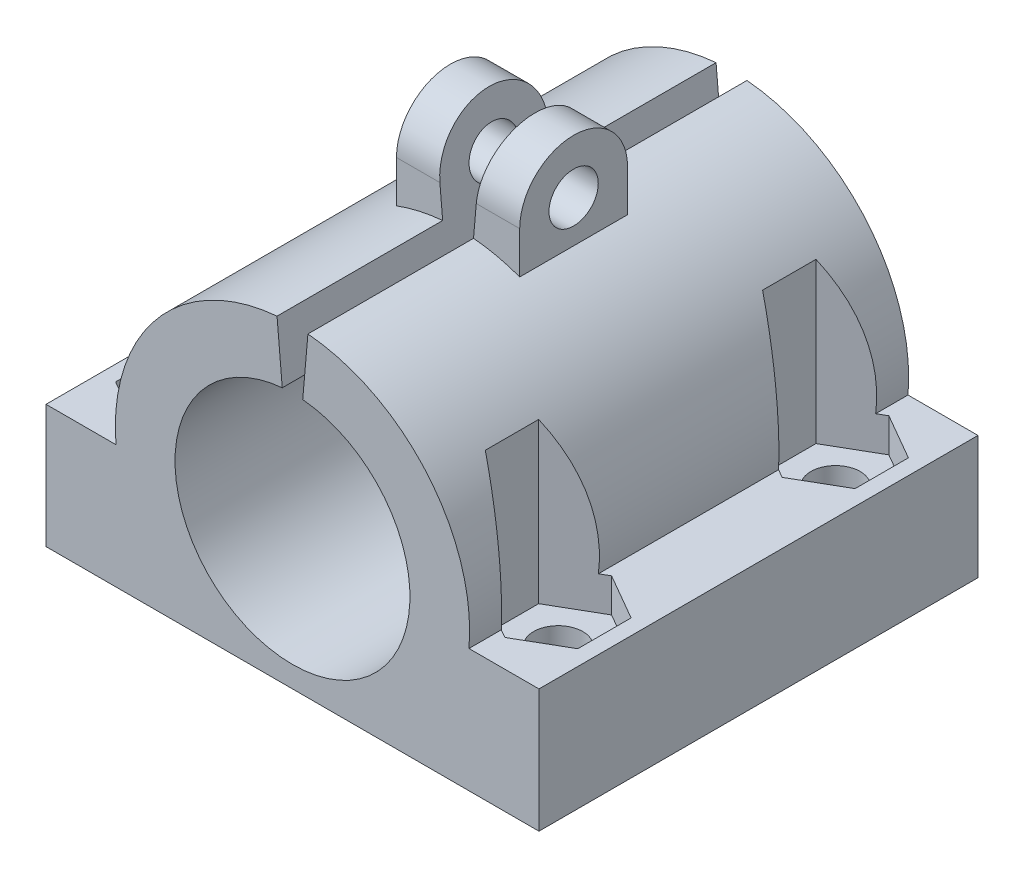
SolidWorks part; units mm, degrees
ref_plane "Front Plane" through (0, 0, 0) normal (0, 0, 1) x (1, 0, 0)
ref_plane "Top Plane" through (0, 0, 0) normal (0, 1, 0) x (1, 0, 0)
ref_plane "Right Plane" through (0, 0, 0) normal (1, 0, 0) x (0, 0, -1)
sketch "Sketch1" plane through (0, 0, 0) normal (0, 1, 0) x (1, 0, 0)
  line L1 (-16, 14.25) -> (16, 14.25)
  line L2 (-16, 14.25) -> (-16, -14.25)
  line L3 (-16, -14.25) -> (16, -14.25)
  line L4 (16, 14.25) -> (16, -14.25)
  line L5 (-16, 14.25) -> (16, -14.25) construction
  line L6 (-16, -14.25) -> (16, 14.25) construction
  point P0 (0, 0)
  dimension "D1" = 32
  dimension "D2" = 28.5
extrude "Boss-Extrude1" add sketch "Sketch1" along normal blind 8
sketch "Sketch3" plane through (0, 0, 14.25) normal (0, 0, 1) x (1, 0, 0)
  line L0 (0, 0) -> (0, 9) construction
  line L1 (-16, 0) -> (16, 0) construction
  line L2 (-7.1589, 0) -> (7.1589, 0)
  arc A0 (7.1589, 0) -> (-7.1589, 0) centre (0, 9) ccw
  dimension "D1" = 23
  dimension "D2" = 9
extrude "Boss-Extrude2" add sketch "Sketch3" against normal through all contours A0 L2
sketch "Sketch4" plane through (0, 0, 14.25) normal (0, 0, 1) x (1, 0, 0)
  line L0 (0, 20.5) -> (0, 0) construction
  line L1 (0, 9) -> (-11.5, 9) construction
  arc A0 (11.4564, 8) -> (-11.4564, 8) centre (0, 9) ccw construction
  circle A1 centre (0, 9) radius 7.625
  dimension "D1" = 15.25
  dimension "D2" = 0
extrude "Cut-Extrude2" cut sketch "Sketch4" against normal offset from surface (26.5 mm away) 2 up to face at (0, 7.4167, -14.25)
sketch "Sketch5" plane through (0, 0, -14.25) normal (0, 0, -1) x (-1, 0, 0)
  line L0 (0, 0) -> (0, 20.5) construction
  line L1 (7.625, 9) -> (-7.625, 9) construction
  arc A0 (11.4564, 8) -> (-11.4564, 8) centre (0, 9) ccw construction
  circle A1 centre (0, 9) radius 5
  circle A2 centre (0, 9) radius 7.625 construction
  circle A3 centre (0, 9) radius 7.625 construction
  dimension "D1" = 10
  dimension "D2" = 0
extrude "Cut-Extrude3" cut sketch "Sketch5" against normal through all
sketch "Sketch2" plane through (0, 8, 0) normal (0, 1, 0) x (1, 0, 0)
  line L0 (0, -14.25) -> (0, 14.25) construction
  line L1 (0, 0) -> (-16, 0) construction
  line L2 (-16, 14.25) -> (-16, -14.25) construction
  line L5 (-11.5, -14.25) -> (11.5, -14.25) construction
  line L6 (11.5, 14.25) -> (-11.5, 14.25) construction
  circle A0 centre (-12, 9) radius 1.6
  circle A1 centre (12, 9) radius 1.6
  circle A2 centre (12, -9) radius 1.6
  circle A3 centre (-12, -9) radius 1.6
  dimension "D3" = 3.2
  dimension "D1" = 12
  dimension "D2" = 9
extrude "Cut-Extrude1" cut sketch "Sketch2" against normal through all and the other way through all
sketch "Sketch6" plane through (0, 8, 0) normal (0, 1, 0) x (1, 0, 0)
  line L0 (-16, 0) -> (16, 0) construction
  line L1 (-16, 14.25) -> (-16, -14.25) construction
  line L2 (16, -14.25) -> (16, 14.25) construction
  line L3 (0, 14.25) -> (0, -14.25) construction
  line L4 (11.5, 14.25) -> (-11.5, 14.25) construction
  line L5 (-11.5, -14.25) -> (11.5, -14.25) construction
  line L6 (-12, 9) -> (-12, 12.4641) construction
  line L7 (-12, 12.4641) -> (-15, 10.7321)
  line L8 (-15, 10.7321) -> (-15, 7.2679)
  line L9 (-15, 7.2679) -> (-12, 5.5359)
  line L10 (-12, 5.5359) -> (-9, 7.2679)
  line L11 (-9, 7.2679) -> (-9, 10.7321)
  line L12 (-9, 10.7321) -> (-12, 12.4641)
  line L13 (-12, -9) -> (-12, -12.4641) construction
  line L14 (-9, -10.7321) -> (-12, -12.4641)
  line L15 (-9, -7.2679) -> (-9, -10.7321)
  line L16 (-12, -5.5359) -> (-9, -7.2679)
  line L17 (-15, -7.2679) -> (-12, -5.5359)
  line L18 (-15, -10.7321) -> (-15, -7.2679)
  line L19 (-12, -12.4641) -> (-15, -10.7321)
  line L20 (12, -9) -> (12, -12.4641) construction
  line L21 (12, 9) -> (12, 12.4641) construction
  line L22 (12, -12.4641) -> (15, -10.7321)
  line L23 (15, -10.7321) -> (15, -7.2679)
  line L24 (15, -7.2679) -> (12, -5.5359)
  line L25 (12, -5.5359) -> (9, -7.2679)
  line L26 (9, -7.2679) -> (9, -10.7321)
  line L27 (9, -10.7321) -> (12, -12.4641)
  line L28 (9, 10.7321) -> (12, 12.4641)
  line L29 (9, 7.2679) -> (9, 10.7321)
  line L30 (12, 5.5359) -> (9, 7.2679)
  line L31 (15, 7.2679) -> (12, 5.5359)
  line L32 (15, 10.7321) -> (15, 7.2679)
  line L33 (12, 12.4641) -> (15, 10.7321)
  circle A0 centre (-12, 9) radius 3 construction
  circle A1 centre (-12, -9) radius 3 construction
  circle A2 centre (12, -9) radius 3 construction
  circle A3 centre (12, 9) radius 3 construction
  circle A4 centre (-12, 9) radius 1.6 construction
  dimension "D2" = 0
  dimension "D1" = 6
extrude "Cut-Extrude4" cut sketch "Sketch6" along normal through all and the other way blind 2.2
sketch "Sketch8" plane through (0, 0, 0) normal (1, 0, 0) x (0, 0, -1)
  line L0 (0, 0) -> (0, 22.5) construction
  line L1 (-3.5, 22.5) -> (-3.5, 18.5)
  line L2 (-3.5, 18.5) -> (3.5, 18.5)
  line L3 (3.5, 18.5) -> (3.5, 22.5)
  line L4 (14.25, 20.5) -> (-14.25, 20.5) construction
  arc A0 (3.5, 22.5) -> (-3.5, 22.5) centre (0, 22.5) ccw
  circle A1 centre (0, 22.5) radius 1.6
  dimension "D1" = 7
  dimension "D4" = 3.2
  dimension "D2" = 2
  dimension "D3" = 4
extrude "Boss-Extrude3" add sketch "Sketch8" along normal blind 4 and the other way blind 4
sketch "Sketch9" plane through (0, 0, 14.25) normal (0, 0, 1) x (1, 0, 0)
  line L0 (0, 31) -> (0, 9) construction
  line L1 (0, 9) -> (1.7431, 28.9239)
  line L2 (0, 9) -> (-1.7431, 28.9239)
  arc A1 (1.7431, 28.9239) -> (-1.7431, 28.9239) centre (0, 9) ccw
  dimension "D2" = 40
  dimension "D1" = 5
extrude "Cut-Extrude5" cut sketch "Sketch9" against normal through all
equation "\"X-ROD-SPACING\"=45"
equation "\"Y-ROD-SPACING\"=75"
equation "\"Z-ROD-SPACING\"=17.5"
equation "\"Y-BED-OFFSET\"=2"
equation "\"Y-BED-ROD-INSET\"=3.5"
equation "\"T-SLOT-NUT-FILLET-RADIUS\"=0.25"
equation "\"T-SLOT-SCREW-SHAFT-RADIUS\"=1.75"
equation "\"T-SLOT-SCREW-SHAFT-CUTOUT-LENGTH\"=10.5"
equation "\"T-SLOT-NUT-DEPTH\"=4.2"
equation "\"T-SLOT-NUT-WIDTH\"=3"
equation "\"T-SLOT-NUT-END-DISTANCE\"=8"
equation "\"ACRYLIC-THICKNESS\"=10"
equation "\"ACRYLIC-THICKNESS2\"=4.5"
equation "\"ACRYLIC-TAB-CUTOUT-SIZE\"=\"ACRYLIC-THICKNESS\"+\"ACRYLIC-TAB-TOLERANCE\"*2"
equation "\"ACRYLIC-TAB-WIDTH\"=\"ACRYLIC-THICKNESS\""
equation "\"ACRYLIC-M3-HOLE\"=3.2"
equation "\"SMOOTHROD-CAP-SCREW-DISTANCE\"=20"
equation "\"FRAME-WIDTH-INNER\"=370"
equation "\"NEMA17-HOLE-SPACING\"=31"
equation "\"NEMA17-CENTRAL-CUTOUT\"=22.5"
equation "\"Z-BRACKET-REACH\"=55"
equation "\"TOP-BRACKET-SPACING\"=40"
equation "\"SMOOTHROD-X-LENGTH\"=350"
equation "\"SMOOTHROD-Y-LENGTH\"=350"
equation "\"SMOOTHROD-Z-LENGTH\"=350"
equation "\"SMOOTHROD-TIGHTENING-HEADROOM\"=1"
equation "\"LEADSCREW-Z-LENGTH\"=300"
equation "\"SCREW-LENGTH-FRAME\"=\"ACRYLIC-THICKNESS\" + 10"
equation "\"SCREW-HEAD-RADIUS\"=6"
equation "\"PRINTED-X-SMOOTHROD-DIAMETER\"=8.2"
equation "\"PRINTED-X-SMOOTHROD-CUTOUT\"=10"
equation "\"PRINTED-X-BASE-HEIGHT\"=10"
equation "\"PRINTED-LM8UU-CUTOUT-SIZE\"=15.25"
equation "\"PRINTED-LM8UU-CUTOUT-LENGTH\"=24.5"
equation "\"PRINTED-X-IDLER-HEIGHT\"=16"
equation "\"PSU-MOUNTING-WIDTH\"=95"
equation "\"PSU-MOUNTING-HEIGHT\"=177"
equation "\"Y-BELT-TO-ROD-DISTANCE\"=20"
equation "\"D3@Sketch2\"=3.2"
equation "\"D1@Sketch4\"=\"PRINTED-LM8UU-CUTOUT-SIZE\""
equation "\"D1@Sketch6\"=\"T-SLOT-NUT-WIDTH\"*2"
